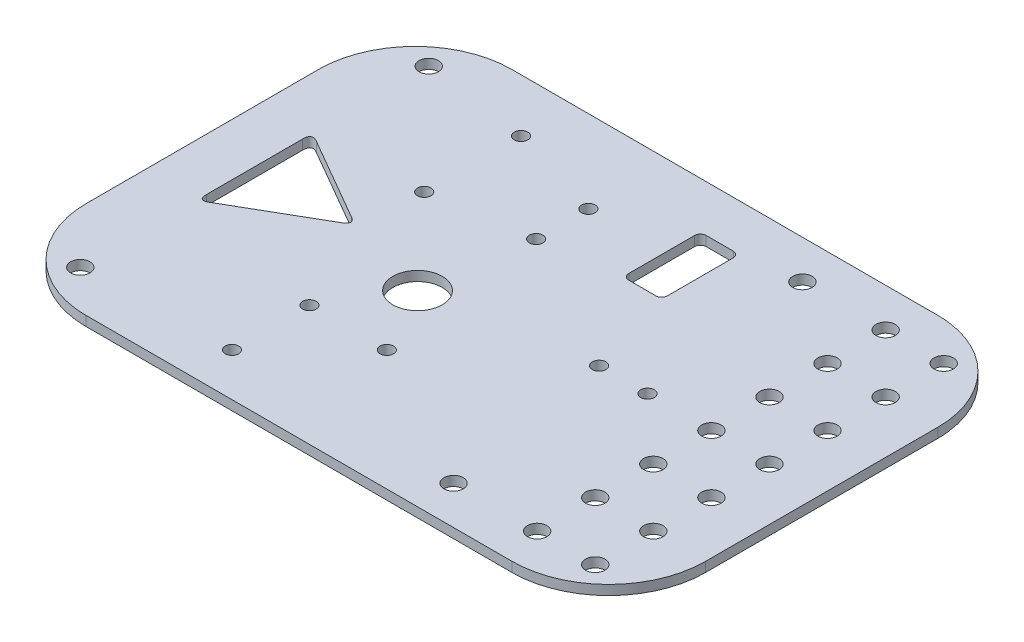
SolidWorks part; units mm, degrees
ref_plane "Front Plane" through (0, 0, 0) normal (0, 0, 1) x (1, 0, 0)
ref_plane "Top Plane" through (0, 0, 0) normal (0, 1, 0) x (1, 0, 0)
ref_plane "Right Plane" through (0, 0, 0) normal (1, 0, 0) x (0, 0, -1)
sketch "Sketch1" plane through (0, 0, 0) normal (0, 1, 0) x (1, 0, 0)
  line L2 (-160, 110) -> (160, 110)
  line L3 (-160, 110) -> (-160, -110)
  line L4 (-160, -110) -> (160, -110)
  line L5 (160, 110) -> (160, -110)
  line L6 (-160, 110) -> (160, -110) construction
  line L7 (-160, -110) -> (160, 110) construction
  point P3 (0, 0)
  dimension "D1" = 320
  dimension "D2" = 220
extrude "the upper chasiss" add sketch "Sketch1" along normal mid plane 5 contours L3 L2 L5 L4
sketch "Sketch2" plane through (0, 0, 0) normal (0, 1, 0) x (1, 0, 0)
  line L0 (160, 0) -> (-160, 0) construction
  line L1 (160, 110) -> (160, -110) construction
  line L2 (-160, 110) -> (-160, -110) construction
  circle A0 centre (70, 0) radius 3.5
  circle A1 centre (45, 0) radius 3.5
  dimension "D1" = 7
  dimension "D2" = 7
  dimension "D3" = 25
  dimension "D4" = 90
extrude "Battary" cut sketch "Sketch2" along normal up to surface and the other way up to surface up to face at (0, 2.5, 0) other way up to face at (0, -2.5, 0)
sketch "Sketch3" plane through (0, 0, 0) normal (0, 1, 0) x (1, 0, 0)
  line L1 (-56.8984, -47.7601) -> (-16.8984, -47.7601) construction
  line L2 (-56.8984, -47.7601) -> (-56.8984, -87.7601) construction
  circle A0 centre (-56.8984, -47.7601) radius 3.5
  circle A1 centre (-16.8984, -47.7601) radius 3.5
  circle A2 centre (-56.8984, -87.7601) radius 3.5
  dimension "D1" = 7
  dimension "D2" = 7
  dimension "D3" = 7
  dimension "D4" = 40
  dimension "D5" = 40
extrude "power section" cut sketch "Sketch3" against normal up to surface and the other way up to surface up to face at (70, -2.5, -3.5) other way up to face at (70, 2.5, -3.5)
sketch "arduino" plane through (0, 0, 0) normal (0, 1, 0) x (1, 0, 0)
  line L0 (-77.9335, 82.5888) -> (-77.9335, 32.5888) construction
  line L1 (-77.9335, 32.5888) -> (-27.9335, 40.3888) construction
  line L2 (-27.9335, 40.3888) -> (-27.9335, 67.3888) construction
  line L3 (-27.9335, 67.3888) -> (-77.9335, 82.5888) construction
  circle A0 centre (-77.9335, 82.5888) radius 3.5
  circle A1 centre (-77.9335, 32.5888) radius 3.5
  circle A2 centre (-27.9335, 67.3888) radius 3.5
  circle A3 centre (-27.9335, 40.3888) radius 3.5
  dimension "D1" = 7
  dimension "D2" = 7
  dimension "D3" = 7
  dimension "D4" = 7
  dimension "D5" = 50
  dimension "D6" = 27
  dimension "D7" = 50
  dimension "D8" = 15.2
extrude "arduino section" cut sketch "arduino" against normal mid plane 5
sketch "Sketch7" plane through (0, 2.5, 0) normal (0, 1, 0) x (1, 0, 0)
  line L0 (-160, 0) -> (160, 0) construction
  line L1 (-160, 110) -> (-160, -110) construction
  line L2 (160, 110) -> (160, -110) construction
  line L3 (0, 110) -> (0, -110) construction
  line L4 (-160, 110) -> (160, 110) construction
  line L5 (-160, -110) -> (160, -110) construction
  line L6 (-133, -90) -> (-133, 0) construction
  line L7 (-133, 90) -> (-133, 0) construction
  line L8 (60, 90) -> (60, -90.1777) construction
  circle A2 centre (-133, -90) radius 5
  circle A3 centre (-133, 90) radius 5
  circle A4 centre (60, -90.1777) radius 5
  circle A5 centre (60, 90) radius 5
  dimension "D1" = 10
  dimension "D2" = 10
  dimension "D5" = 10
  dimension "D6" = 10
  dimension "D3" = 20
  dimension "D4" = 27
  dimension "D7" = 100
extrude "link nails" cut sketch "Sketch7" against normal mid plane 10
sketch "Sketch9" plane through (0, 2.5, 0) normal (0, 1, 0) x (1, 0, 0)
  line L0 (160, 0) -> (-160, 0) construction
  line L1 (160, 110) -> (160, -110) construction
  line L2 (-160, 110) -> (-160, -110) construction
  line L4 (11.3906, 85.9212) -> (31.3906, 85.9212)
  line L5 (11.3906, 85.9212) -> (11.3906, 45.9212)
  line L6 (11.3906, 45.9212) -> (31.3906, 45.9212)
  line L7 (31.3906, 85.9212) -> (31.3906, 45.9212)
  line L8 (11.3906, 85.9212) -> (31.3906, 45.9212) construction
  line L9 (11.3906, 45.9212) -> (31.3906, 85.9212) construction
  point P6 (126.2109, 0)
  dimension "D1" = 20
  dimension "D2" = 40
extrude "rect cut" cut sketch "Sketch9" against normal mid plane 10
sketch "Sketch10" plane through (0, 2.5, 0) normal (0, 1, 0) x (1, 0, 0)
  circle A0 centre (-35.5184, -13.2763) radius 12.759
extrude "circ cut" cut sketch "Sketch10" against normal mid plane 10
fillet "Fillet4" radius 50 4 edges at (-160, 0, 110) (160, 0, 110) (160, 0, -110) (-160, 0, -110) first distance on face at (0, 0, 110) first distance on face at (0, 0, -110)
sketch "Sketch11" plane through (0, 0, 0) normal (0, 1, 0) x (1, 0, 0)
  line L6 (-133, 90) -> (197.2842, 90) construction
  line L7 (-110, 110) -> (110, 110) construction
  line L9 (160, 60) -> (160, -60) construction
  line L10 (-133, -90) -> (197.2842, -90) construction
  circle A2 centre (133, 90) radius 5
  dimension "D1" = 20
  dimension "D2" = 10
  dimension "D3" = 27
extrude "Cut-Extrude1" cut sketch "Sketch11" against normal mid plane 10
pattern_linear "LPattern1" count 7 spacing 30 along (0, 0, 1) count 2 spacing 30 along (-1, 0, 0) of "Cut-Extrude1"
fillet "Fillet5" radius 3 4 edges at (11.3906, 0, -45.9212) (31.3906, 0, -45.9212) (11.3906, 0, -85.9212) (31.3906, 0, -85.9212)
sketch "Sketch13" plane through (0, 0, 0) normal (0, 1, 0) x (1, 0, 0)
  line L0 (-133, 90) -> (-133, -90) construction
  line L1 (-160, 0) -> (160, 0) construction
  line L2 (-160, 60) -> (-160, -60) construction
  line L3 (160, 60) -> (160, -60) construction
  line L4 (-133, 30) -> (-81.0385, 0)
  line L5 (-81.0385, 0) -> (-133, -30)
  line L6 (-133, -30) -> (-133, 30)
  dimension "D1" = 60
extrude "Cut-Extrude2" cut sketch "Sketch13" against normal mid plane 10
fillet "Fillet6" radius 3 3 edges at (-133, 0, 30) (-81.0385, 0, 0) (-133, 0, -30) curvature continuous yes
equation "\"carWidth\"= 22cm'the car full width"
equation "\"carLong\"= 32cm"
equation "\"D2@Sketch1\"=\"carWidth\""
equation "\"D1@Sketch1\"=\"carLong\""
equation "\"chasissTheikness\"= 0.5cm"
equation "\"D1@the upper chasiss\"=\"chasissTheikness\" "
equation "\"battaryMargin\"= 25mm'the width between the two battary nails"
equation "\"battaryNailsDiam\"= 7mm'battary Nails Diameters"
equation "\"D1@Sketch2\"=\"battaryNailsDiam\""
equation "\"D2@Sketch2\"=\"battaryNailsDiam\""
equation "\"D3@Sketch2\"=\"battaryMargin\""
equation "\"powerWidht\"= 40mm"
equation "\"powerNailDiam\"= 7mm"
equation "\"D1@Sketch3\"=\"powerNailDiam\""
equation "\"D2@Sketch3\"=\"powerNailDiam\""
equation "\"D3@Sketch3\"=\"powerNailDiam\""
equation "\"D4@Sketch3\"=\"powerWidht\""
equation "\"D5@Sketch3\"=\"powerWidht\""
equation "\"arduinoTopWidth\"= 50mm'the width between nails"
equation "\"arduinoBottomWidth\"= 27mm'the width between nails"
equation "\"arduinoNailsDiam\"= 7mm'the nail diameter"
equation "\"D1@arduino\" = \"arduinoNailsDiam\""
equation "\"D2@arduino\" = \"arduinoNailsDiam\""
equation "\"D3@arduino\" = \"arduinoNailsDiam\""
equation "\"D4@arduino\" = \"arduinoNailsDiam\""
equation "\"D5@arduino\" = \"arduinoTopWidth\""
equation "\"D6@arduino\" = \"arduinoBottomWidth\""
equation "\"D7@arduino\" = \"arduinoTopWidth\""
equation "\"arduinoTobBottomShift\"= 15.2mm"
equation "\"D8@arduino\" = \"arduinoTobBottomShift\""
equation "\"chasissNailsDiam\"= 10mm"
equation "\"D2@Sketch7\"=\"chasissNailsDiam\""
equation "\"D1@Sketch7\"=\"chasissNailsDiam\""
equation "\"D5@Sketch7\"=\"chasissNailsDiam\""
equation "\"D6@Sketch7\"=\"chasissNailsDiam\""
equation "\"10ةة\"=12.1958"
